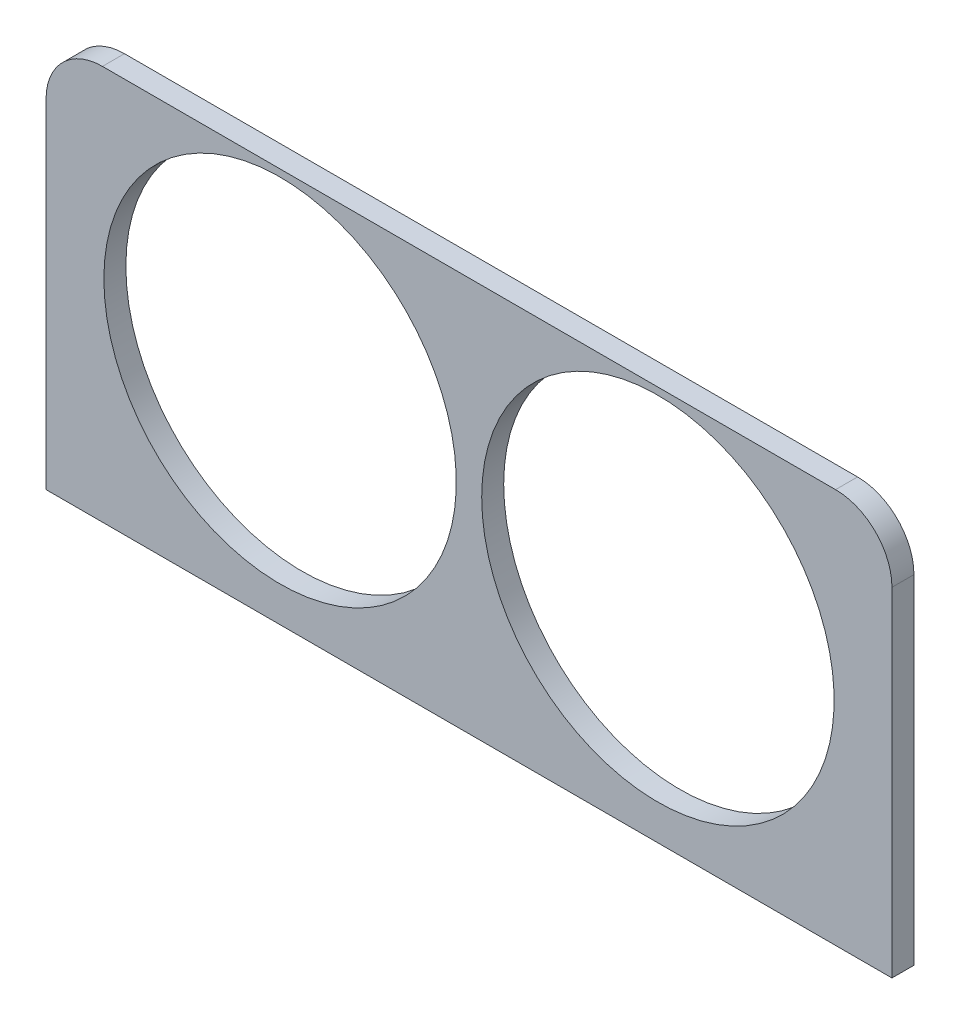
SolidWorks part; units mm, degrees
ref_plane "Front Plane" through (0, 0, 0) normal (0, 0, 1) x (1, 0, 0)
ref_plane "Top Plane" through (0, 0, 0) normal (0, 1, 0) x (1, 0, 0)
ref_plane "Right Plane" through (0, 0, 0) normal (1, 0, 0) x (0, 0, -1)
sketch "Sketch1" plane through (0, 0, 0) normal (0, 0, 1) x (1, 0, 0)
  line L0 (-6.7, 0.5) -> (6.7, 0.5) construction
  line L1 (-15, -7) -> (15, -7)
  line L2 (-15, -7) -> (-15, 7)
  line L3 (-15, 7) -> (15, 7)
  line L4 (15, -7) -> (15, 7)
  line L5 (-15, -7) -> (15, 7) construction
  line L6 (-15, 7) -> (15, -7) construction
  line L7 (-15, 0.5) -> (15, 0.5) construction
  circle A0 centre (-6.7, 0.5) radius 6.25
  circle A1 centre (6.7, 0.5) radius 6.25
  point P4 (0, 0)
  point P5 (0, 0)
  point P6 (0, 0.5)
  dimension "D1" = 12.5
  dimension "D2" = 13.4
  dimension "D3" = 6.5
  dimension "D4" = 30
  dimension "D5" = 14
extrude "Boss-Extrude1" add sketch "Sketch1" along normal blind 0.78
fillet "Fillet1" radius 2 2 edges at (15, 7, 0.39) (-15, 7, 0.39)
